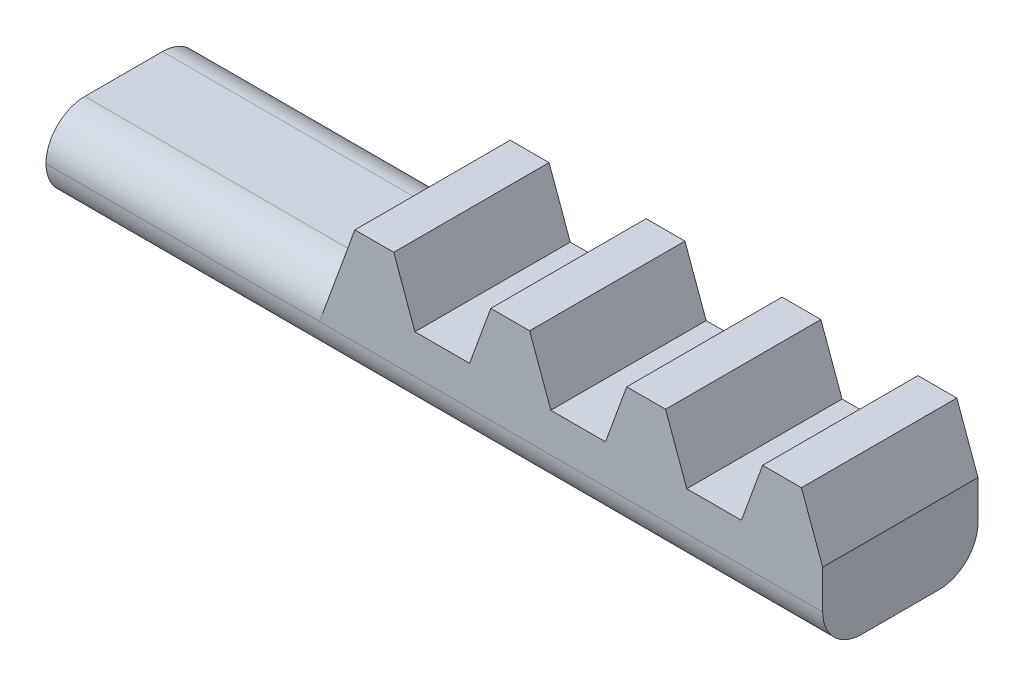
SolidWorks part; units mm, degrees
ref_plane "Front Plane" through (0, 0, 0) normal (0, 0, 1) x (1, 0, 0)
ref_plane "Top Plane" through (0, 0, 0) normal (0, 1, 0) x (1, 0, 0)
ref_plane "Right Plane" through (0, 0, 0) normal (1, 0, 0) x (0, 0, -1)
sketch "Sketch1" plane through (0, 0, 0) normal (0, 0, 1) x (1, 0, 0)
  line L0 (10, 1) -> (9.454, 2.5)
  line L1 (-10, -1) -> (10, -1)
  line L2 (-10, -1) -> (-10, 1)
  line L3 (-10, 1) -> (-2.5919, 1)
  line L4 (10, -1) -> (10, 1)
  line L7 (9.454, 2.5) -> (8.454, 2.5)
  line L8 (8.454, 2.5) -> (7.9081, 1)
  line L9 (6.5, 1) -> (5.954, 2.5)
  line L10 (5.954, 2.5) -> (4.954, 2.5)
  line L11 (4.954, 2.5) -> (4.4081, 1)
  line L12 (-13.5, 1) -> (-2.5919, 1)
  line L13 (3, 1) -> (2.454, 2.5)
  line L14 (2.454, 2.5) -> (1.454, 2.5)
  line L15 (1.454, 2.5) -> (0.9081, 1)
  line L16 (-17, 1) -> (-2.5919, 1)
  line L17 (-0.5, 1) -> (-1.046, 2.5)
  line L18 (-1.046, 2.5) -> (-2.046, 2.5)
  line L19 (-2.046, 2.5) -> (-2.5919, 1)
  line L20 (-20.5, 1) -> (-2.5919, 1)
  line L21 (-0.5, 1) -> (0.9081, 1)
  line L22 (-0.5, 1) -> (0.9081, 1)
  line L23 (-0.5, 1) -> (0.9081, 1)
  line L24 (3, 1) -> (4.4081, 1)
  line L25 (3, 1) -> (4.4081, 1)
  line L26 (6.5, 1) -> (7.9081, 1)
  point P0 (0, 0)
  dimension "D1" = 2
  dimension "D2" = 20
  dimension "D3" = 1
  dimension "D4" = 110
  dimension "D5" = 110
  dimension "D6" = 1.5
  dimension "D7" = 4
extrude "Boss-Extrude1" add sketch "Sketch1" along normal blind 4 contours L26 L9 L10 L11 L24 L13 L14 L15 L21 L17 L18 L19 L3 L2 L1 L4 L0 L7 L8 region at (0.6973, 0.3128, 0)
fillet "Fillet1" radius 1 4 edges at (0, -1, 4) (0, -1, 0) (-6.296, 1, 0) (-6.296, 1, 4)
